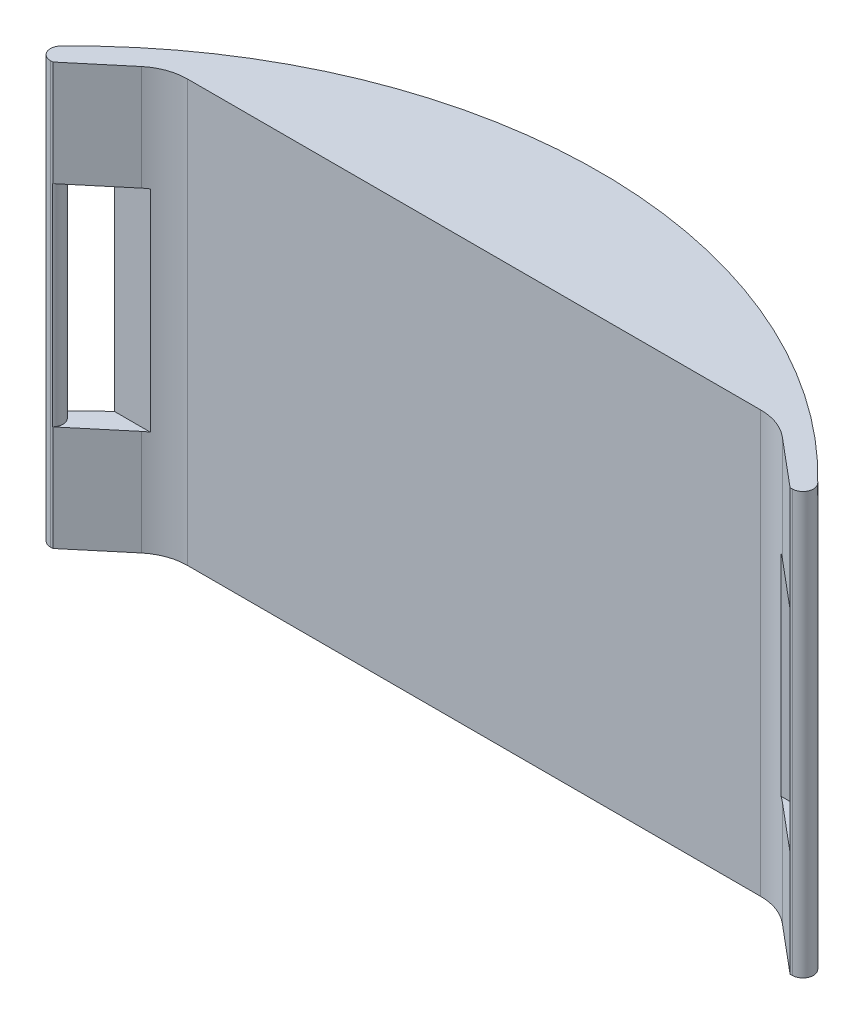
SolidWorks part; units mm, degrees
ref_plane "前视基准面" through (0, 0, 0) normal (0, 0, 1) x (1, 0, 0)
ref_plane "上视基准面" through (0, 0, 0) normal (0, 1, 0) x (1, 0, 0)
ref_plane "右视基准面" through (0, 0, 0) normal (1, 0, 0) x (0, 0, -1)
sketch "草图1" plane through (0, 0, 0) normal (0, 1, 0) x (1, 0, 0)
  line L3 (-58.4308, -54.9577) -> (91.5692, -54.9577)
  arc A0 (91.5692, -54.9577) -> (-58.4308, -54.9577) centre (16.5692, -121.1014) ccw
extrude "凸台-拉伸4" add sketch "草图1" along normal blind 80 contours L3 A0
sketch "草图6" plane through (0, 80, 0) normal (0, 1, 0) x (1, 0, 0)
  line L0 (16.5692, -54.9577) -> (-53.4308, -54.9577)
  line L1 (86.5692, -54.9577) -> (77.4225, -47.293)
  line L2 (-53.4308, -54.9577) -> (-44.2841, -47.293)
  line L3 (-58.4308, -54.9577) -> (91.5692, -54.9577) construction
  line L4 (16.5692, -54.9577) -> (86.5692, -54.9577)
  line L6 (16.5692, -44.9577) -> (-37.8613, -44.9577)
  line L7 (16.5692, -44.9577) -> (70.9997, -44.9577)
  arc A1 (-44.2841, -47.293) -> (-37.8613, -44.9577) centre (-37.8613, -54.9577) cw
  arc A2 (70.9997, -44.9577) -> (77.4225, -47.293) centre (70.9997, -54.9577) cw
  dimension "D1" = 10
extrude "切除-拉伸1" cut sketch "草图6" against normal blind 80
fillet "圆角3" radius 2 1 edges at (-58.4308, 40, 54.9577)
fillet "圆角4" radius 2 1 edges at (91.5692, 40, 54.9577)
sketch "草图7" plane through (0, 0, 0) normal (1, 0, 0) x (0, 0, -1)
  line L0 (-34.9577, 20) -> (-21.1014, 20)
  line L2 (-34.9577, 40) -> (-34.9577, 60)
  line L3 (-34.9577, 40) -> (-34.9577, 20)
  line L4 (-21.1014, 0) -> (-21.1014, 80) construction
  line L5 (-21.1014, 20) -> (-21.1014, 60)
  line L6 (-21.1014, 60) -> (-34.9577, 60)
extrude "切除-拉伸2" cut sketch "草图7" against normal mid plane 180
sketch "草图8" plane through (0, 0, 0) normal (1, 0, 0) x (0, 0, -1)
  line L1 (-51.567, 0) -> (-51.567, 80) construction
  line L2 (-46.567, 40) -> (-46.567, 20)
  line L3 (-46.567, 40) -> (-46.567, 60)
  line L4 (-46.567, 60) -> (-51.567, 60)
  line L5 (-51.567, 60) -> (-51.567, 40)
  line L6 (-51.567, 20) -> (-46.567, 20)
  line L7 (-51.567, 20) -> (-51.567, 40)
extrude "切除-拉伸3" cut sketch "草图8" against normal mid plane 180
fillet "圆角5" radius 2 1 edges at (-49.3845, 40, 51.567)
fillet "圆角6" radius 2 1 edges at (82.5229, 40, 51.567)
